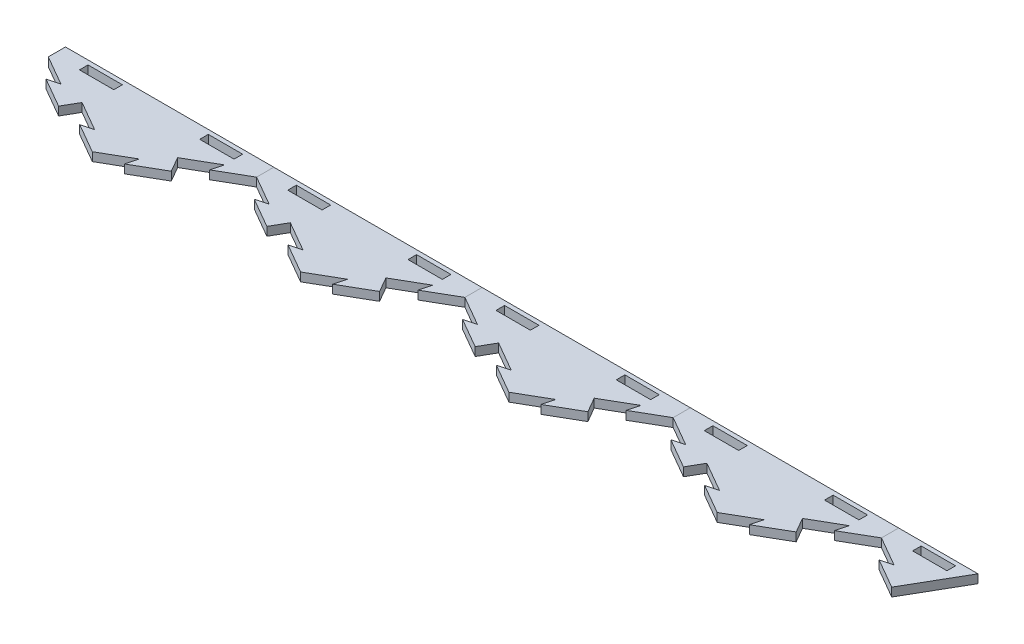
SolidWorks part; units mm, degrees
material "Cedar"
ref_plane "Front Plane" through (0, 0, 0) normal (0, 0, 1) x (1, 0, 0)
ref_plane "Top Plane" through (0, 0, 0) normal (0, 1, 0) x (1, 0, 0)
ref_plane "Right Plane" through (0, 0, 0) normal (1, 0, 0) x (0, 0, -1)
sketch "Sketch1" plane through (0, 0, 0) normal (0, 1, 0) x (1, 0, 0)
  line L0 (-76.9897, 0) -> (76.9897, 0) construction
  line L1 (-76.9897, 0) -> (0, -44.45)
  line L2 (0, -44.45) -> (76.9897, 0)
  line L3 (76.9897, 0) -> (76.9897, 88.9)
  line L4 (76.9897, 88.9) -> (0, 133.35)
  line L5 (0, 133.35) -> (-76.9897, 88.9)
  line L6 (-76.9897, 88.9) -> (-76.9897, 0)
  line L7 (0, -44.45) -> (0, 44.45) construction
  circle A0 centre (0, 44.45) radius 76.9897 construction
  point P9 (0, 0)
  dimension "D1" = 88.9
extrude "Boss-Extrude1" add sketch "Sketch1" against normal blind 6.35
sketch "Sketch2" plane through (0, 0, 0) normal (0, 1, 0) x (1, 0, 0)
  line L0 (-76.9897, 44.45) -> (76.9897, 44.45) construction
  line L1 (-76.9897, 88.9) -> (-76.9897, 0) construction
  line L2 (76.9897, 0) -> (76.9897, 88.9) construction
  point P2 (0, 44.45)
ref_axis "Axis1" through (0, 0, -44.45) along (0, 1, 0)
sketch "Sketch10" plane through (0, 0, 0) normal (0, 1, 0) x (1, 0, 0)
  line L0 (0, -44.45) -> (-21.997, -31.75) construction
  line L1 (-21.997, -31.75) -> (-13.3228, -29.4257)
  line L2 (-13.3228, -29.4257) -> (-35.3198, -16.7257)
  line L3 (-35.3198, -16.7257) -> (-38.4948, -22.225)
  line L4 (-21.997, -31.75) -> (-38.4948, -22.225)
  line L5 (-76.9897, 0) -> (0, -44.45) construction
  dimension "D1" = 45
  dimension "D2" = 6.35
extrude "Cut-Extrude4" cut sketch "Sketch10" against normal through all
sketch "Sketch11" plane through (0, 0, 0) normal (0, 1, 0) x (1, 0, 0)
  line L0 (-38.4948, -22.225) -> (-76.9897, 0) construction
  line L1 (-38.4948, -22.225) -> (-41.6698, -27.7243)
  line L2 (-41.6698, -27.7243) -> (-63.6669, -15.0243)
  line L3 (-63.6669, -15.0243) -> (-54.9926, -12.7)
  line L4 (-54.9926, -12.7) -> (-38.4948, -22.225)
  line L5 (-54.9926, -12.7) -> (-76.9897, 0) construction
  line L6 (-54.9926, -12.7) -> (-76.9897, 0) construction
  line L7 (-76.9897, 0) -> (-38.4948, -22.225) construction
  line L8 (-76.9897, 88.9) -> (-76.9897, 0) construction
  dimension "D1" = 45
  dimension "D2" = 6.35
extrude "Boss-Extrude4" add sketch "Sketch11" against normal blind 6.35
pattern_circular "CirPattern1" count 2 every 60 about axis through (0, 0, -44.45) along (0, 1, 0) of "Cut-Extrude4", "Boss-Extrude4"
sketch "Sketch12" plane through (0, 0, 0) normal (0, 1, 0) x (1, 0, 0)
  line L0 (-76.9897, 12.7) -> (76.9897, 12.7)
  line L1 (-76.9897, 88.9) -> (-76.9897, 0) construction
  line L2 (76.9897, 0) -> (76.9897, 88.9) construction
  line L3 (76.9897, 12.7) -> (76.9897, 133.35)
  line L4 (76.9897, 133.35) -> (-76.9897, 133.35)
  line L5 (-76.9897, 133.35) -> (-76.9897, 12.7)
  line L6 (0, 0) -> (0, 12.7) construction
  dimension "D1" = 12.7
extrude "Cut-Extrude5" cut sketch "Sketch12" against normal through all
sketch "Sketch13" plane through (0, 0, 0) normal (0, 1, 0) x (1, 0, 0)
  line L0 (0, 0) -> (0, 12.7) construction
  line L1 (-76.9897, 12.7) -> (76.9897, 12.7) construction
  line L2 (-44.45, 6.35) -> (44.45, 6.35) construction
  line L4 (-57.15, 9.525) -> (-31.75, 9.525)
  line L5 (-57.15, 9.525) -> (-57.15, 3.175)
  line L6 (-57.15, 3.175) -> (-31.75, 3.175)
  line L7 (-31.75, 9.525) -> (-31.75, 3.175)
  line L8 (-57.15, 9.525) -> (-31.75, 3.175) construction
  line L9 (-57.15, 3.175) -> (-31.75, 9.525) construction
  line L10 (31.75, 9.525) -> (57.15, 9.525)
  line L11 (31.75, 9.525) -> (31.75, 3.175)
  line L12 (31.75, 3.175) -> (57.15, 3.175)
  line L13 (57.15, 9.525) -> (57.15, 3.175)
  line L14 (31.75, 9.525) -> (57.15, 3.175) construction
  line L15 (31.75, 3.175) -> (57.15, 9.525) construction
  point P7 (0, 6.35)
  point P8 (0, 6.35)
  dimension "D1" = 6.35
  dimension "D2" = 25.4
  dimension "D3" = 6.35
  dimension "D4" = 25.4
  dimension "D5" = 88.9
extrude "Cut-Extrude6" cut sketch "Sketch13" against normal through all
pattern_linear "LPattern1" count 5 spacing 153.9793 along (1, 0, 0) count 2 spacing 153.9793 along (-1, 0, 0) pattern seed only yes of bodies 136 131
sketch "Sketch14" plane through (0, 0, 0) normal (0, 1, 0) x (1, 0, 0)
  line L0 (615.9173, -44.45) -> (615.9173, 12.7)
  line L1 (538.9276, 12.7) -> (692.9069, 12.7) construction
  line L2 (615.9173, 12.7) -> (692.9069, 12.7)
  line L3 (692.9069, 12.7) -> (692.9069, -44.45)
  line L4 (692.9069, -44.45) -> (615.9173, -44.45)
  line L5 (-153.9793, -44.45) -> (-153.9793, 12.7)
  line L6 (-230.969, 12.7) -> (-76.9897, 12.7) construction
  line L7 (-153.9793, 12.7) -> (-230.969, 12.7)
  line L8 (-230.969, 12.7) -> (-230.969, -44.45)
  line L9 (-230.969, -44.45) -> (-153.9793, -44.45)
  line L10 (580.5974, -16.7257) -> (597.5864, 12.7)
  line L11 (597.5864, 12.7) -> (615.9173, 12.7)
  line L12 (580.5974, -16.7257) -> (574.2474, -27.7243)
  line L13 (574.2474, -27.7243) -> (615.9173, -44.45)
  line L14 (-112.3095, -27.7243) -> (-135.6484, 12.7)
  line L15 (-135.6484, 12.7) -> (-153.9793, 12.7)
  line L16 (-112.3095, -27.7243) -> (-134.3065, -40.4243)
  line L17 (-134.3065, -40.4243) -> (-153.9793, -44.45)
  line L18 (-118.6595, -16.7257) -> (-112.3095, -27.7243) construction
  line M5 (673.0673, 9.525) -> (673.0673, 3.175)
  line M6 (673.0673, 3.175) -> (647.6673, 3.175)
  line M7 (647.6673, 3.175) -> (647.6673, 9.525)
  line M8 (647.6673, 9.525) -> (673.0673, 9.525)
  line M13 (692.9069, 12.7) -> (538.9276, 12.7)
  line M19 (580.5974, -16.7257) -> (602.5945, -29.4257)
  line M20 (602.5945, -29.4257) -> (593.9202, -31.75)
  line M21 (593.9202, -31.75) -> (615.9173, -44.45)
  line M22 (615.9173, -44.45) -> (637.9143, -31.75)
  line M23 (637.9143, -31.75) -> (635.5901, -40.4243)
  line M24 (635.5901, -40.4243) -> (657.5871, -27.7243)
  line M25 (657.5871, -27.7243) -> (651.2371, -16.7257)
  line M26 (651.2371, -16.7257) -> (673.2341, -4.0257)
  line M27 (673.2341, -4.0257) -> (670.9099, -12.7)
  line M28 (670.9099, -12.7) -> (692.9069, 0)
  line M29 (692.9069, 0) -> (692.9069, 12.7)
extrude "Cut-Extrude7" cut sketch "Sketch14" against normal through all contours L17 L16 L14 L15 L5 | L10 L0 M19 M20 M21 M13 | L0 M22 M23 M24 M25 M26 M27 M28 M29 M13 M8 M5 M6 M7 | L8 L9 L5 L7 region at (603.1355, 0, 12.4572) region at (644.4492, 0, 8.9256) region at (-192.4741, 0, 15.875) region at (-138.3884, 0, 16.3957)
sketch "Sketch15" plane through (0, 0, 0) normal (0, 1, 0) x (1, 0, 0)
  line L0 (-135.6484, 12.7) -> (-76.9897, 12.7)
  line L1 (-76.9897, 12.7) -> (-76.9897, -16.7257)
  line L2 (-76.9897, -16.7257) -> (-135.6484, -16.7257)
  line L3 (-135.6484, -16.7257) -> (-135.6484, 12.7)
extrude "Cut-Extrude8" cut sketch "Sketch15" against normal through all
